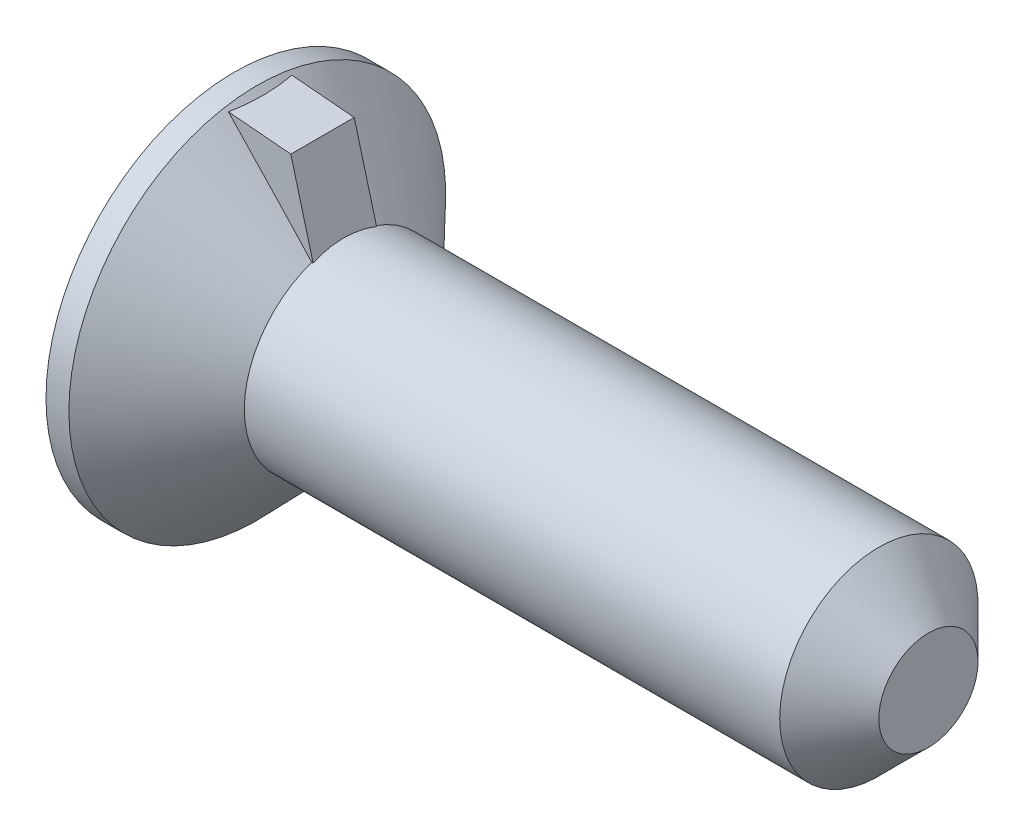
SolidWorks part; units mm, degrees
ref_plane "Front Plane" through (0, 0, 0) normal (0, 0, 1) x (1, 0, 0)
ref_plane "Top Plane" through (0, 0, 0) normal (0, 1, 0) x (1, 0, 0)
ref_plane "Right Plane" through (0, 0, 0) normal (1, 0, 0) x (0, 0, -1)
sketch "BodySke" plane through (0, 0, 0) normal (0, 0, 1) x (1, 0, 0)
  line L0 (0, 0) -> (44.1549, 0) construction
  line L1 (0, 0) -> (0, 9.5)
  line L2 (0, 9.5) -> (1.1544, 9.5)
  line L3 (1.1544, 9.5) -> (5.5, 5)
  line L4 (5.5, 5) -> (32.5, 5)
  line L5 (32.5, 5) -> (35, 2.5)
  line L6 (35, 2.5) -> (35, 0)
  line L7 (35, 0) -> (0, 0)
  line L8 (0, -9.5) -> (1.1544, -9.5) construction
  line L9 (1.1544, -9.5) -> (5.5, -5) construction
  line L10 (5.5, 5) -> (5.5, 0) construction
  line L11 (33.5, 0) -> (33.5, 5) construction
  line L12 (5.5, 5) -> (5.5, 13.4) construction
  line L13 (1.4441, 9.2) -> (4.445, 8.9375) construction
  line L14 (4.445, 8.9375) -> (5.5, 5) construction
  line L15 (1.4441, 9.2) -> (5.5, 9.2) construction
  point P19 (0, 4.172)
  dimension "D2" = 15
  dimension "D3" = 5
  dimension "Thread_minor" = 8.344
  dimension "Head_Height" = 5.5
  dimension "Advance" = 1.5
revolve "BaseBody" add sketch "BodySke" angle 360 about L0
cosmetic thread "ThreadCosmetic" [suppressed] parameters "Thread_minor"=8.344
sketch "NibSke" plane through (0, 0, 0) normal (0, 0, 1) x (1, 0, 0)
  line L0 (4.445, 8.9375) -> (6.8397, 0)
  line L1 (35, 0) -> (0, 0) construction
  line L2 (6.8397, 0) -> (1.1544, 0)
  line L5 (1.1544, 9.2253) -> (4.445, 8.9375)
  line L6 (4.445, 8.9375) -> (5.5, 5) construction
  line L7 (1.4441, 9.2) -> (4.445, 8.9375) construction
  line L8 (1.1544, 9.2253) -> (1.1544, 0)
  line L9 (1.1544, 9.5) -> (1.1544, -9.5) construction
extrude "Nib" add sketch "NibSke" along normal mid plane 3.2
sketch "ThdSchSke" plane through (0, 0, 0) normal (0, 0, 1) x (1, 0, 0)
  line L0 (0, 0) -> (35.8559, 0) construction
  line L1 (0, 9.5) -> (0, -9.5) construction
  line L2 (31, 5.9561) -> (31, 5)
  line L3 (31, 5.9561) -> (31.9561, 5.9561)
  line L4 (31.9561, 5.9561) -> (31.9561, 5)
  line L5 (31.9561, 5) -> (31.478, 4.172)
  line L6 (31.478, 4.172) -> (31, 5)
  dimension "D1" = 1.5
revolve "ThreadSchematic" [suppressed] cut sketch "ThdSchSke" angle 360 about L0
pattern_linear "ThdSchPat" [suppressed] of bodies 115
equation "\"Thread_minor@ThreadCosmetic\" = \"Thread_minor@BodySke\""
equation "\"D1@ThdSchSke\" = \"Advance@BodySke\""
equation "\"Advance@ThdSchPat\" = \"Advance@BodySke\""
equation "\"Teeth_Num@ThdSchPat\" =  int( (  \"Thread_length@BodySke\" - \"Depth_Chamfer@BodySke\" )  / \"Advance@BodySke\" )  - 1"
